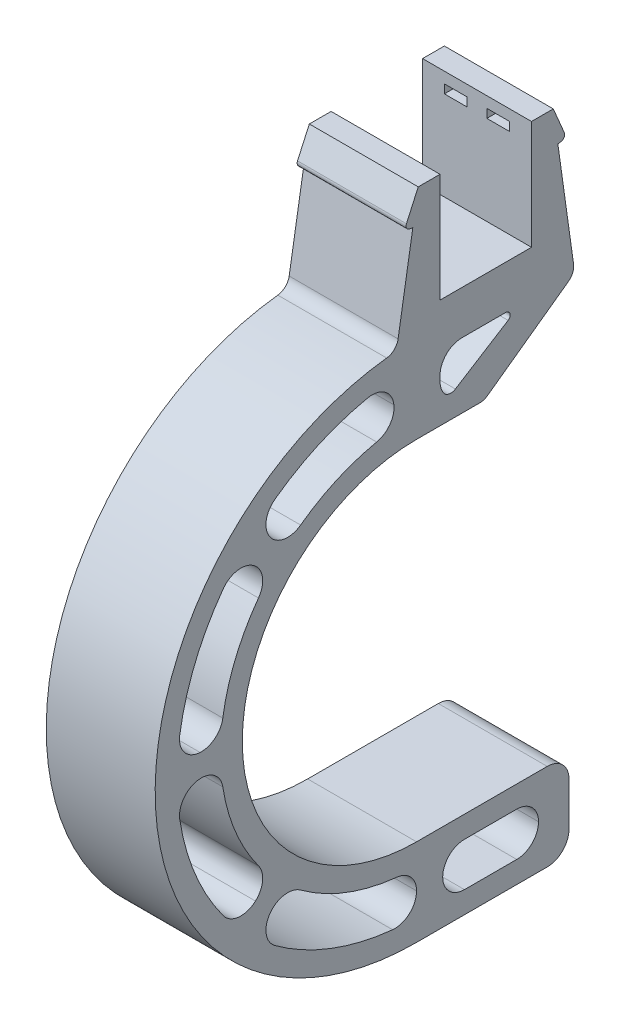
SolidWorks part; units mm, degrees
ref_plane "Front Plane" through (0, 0, 0) normal (0, 0, 1) x (1, 0, 0)
ref_plane "Top Plane" through (0, 0, 0) normal (0, 1, 0) x (1, 0, 0)
ref_plane "Right Plane" through (0, 0, 0) normal (1, 0, 0) x (0, 0, -1)
sketch "Sketch1" plane through (0, 0, 0) normal (1, 0, 0) x (0, 0, -1)
  line L0 (-10.1154, 7.5) -> (-10.1154, 32.5148)
  line L1 (-10.1154, 7.5) -> (10.8846, 7.5)
  line L2 (-15.5, -17.5) -> (0, -17.5)
  line L3 (0, -17.5) -> (20.8, -2.5)
  line L4 (-10.1154, -12.7739) -> (-10.1154, -2.5)
  line L5 (-15.1154, 32.5148) -> (-20.1154, 2.3222)
  line L6 (-15.5, -102.5) -> (-15.5, -112.5)
  line L7 (-10.1154, -2.5) -> (8.4637, -2.5)
  line L8 (8.4637, -2.5) -> (-7.9175, -12.7739)
  line L9 (-15.1154, 32.5148) -> (-10.1154, 32.5148)
  line L10 (15.8846, 32.5148) -> (20.8, -2.5)
  line L11 (-7.9175, -12.7739) -> (-10.1154, -12.7739)
  line L12 (-60.4383, -59.8551) -> (-70.4246, -60.3785)
  line L13 (15.8846, 32.5148) -> (10.8846, 32.5148)
  line L14 (-60.4383, -55.1449) -> (-70.4246, -54.6215)
  line L15 (10.8846, 7.5) -> (10.8846, 32.5148)
  line L16 (-48.9415, -27.3891) -> (-56.373, -20.6978)
  line L17 (-15.5, -117.5) -> (19.5, -117.5)
  line L18 (-15.5, -112.5) -> (-15.5, -102.5)
  line L19 (-15.5, -97.5) -> (19.5, -97.5)
  line L20 (19.5, -117.5) -> (19.5, -97.5)
  line L21 (-45.6109, -24.0585) -> (-52.3022, -16.627)
  line L22 (-20.2038, -12.7465) -> (-21.2491, -2.8013)
  line L23 (-48.9415, -87.6109) -> (-56.373, -94.3022)
  line L24 (-45.6109, -90.9415) -> (-52.3022, -98.373)
  line L26 (-9.5, -102.5) -> (12.5, -102.5)
  line L27 (-9.5, -102.5) -> (-9.5, -112.5)
  line L28 (-9.5, -112.5) -> (12.5, -112.5)
  line L29 (12.5, -102.5) -> (12.5, -112.5)
  arc A0 (-20.1154, 2.3222) -> (-15.5, -117.5) centre (-15.5, -57.5) ccw
  arc A1 (-15.5, -17.5) -> (-15.5, -97.5) centre (-15.5, -57.5) ccw
  arc A2 (-20.2038, -12.7465) -> (-45.6109, -24.0585) centre (-15.5, -57.5) ccw
  arc A3 (-21.2491, -2.8013) -> (-52.3022, -16.627) centre (-15.5, -57.5) ccw
  arc A4 (-48.9415, -27.3891) -> (-60.4383, -55.1449) centre (-15.5, -57.5) ccw
  arc A5 (-56.373, -20.6978) -> (-70.4246, -54.6215) centre (-15.5, -57.5) ccw
  arc A6 (-45.6109, -90.9415) -> (-15.5, -102.5) centre (-15.5, -57.5) ccw
  arc A7 (-52.3022, -98.373) -> (-15.5, -112.5) centre (-15.5, -57.5) ccw
  arc A8 (-70.4246, -60.3785) -> (-56.373, -94.3022) centre (-15.5, -57.5) ccw
  arc A9 (-60.4383, -59.8551) -> (-48.9415, -87.6109) centre (-15.5, -57.5) ccw
  point P0 (0, 0)
  dimension "D7" = 120
  dimension "D9" = 20
  dimension "D5" = 5
  dimension "D6" = 5
  dimension "D2" = 21
  dimension "D3" = 5
  dimension "D4" = 5
  dimension "D8" = 65
  dimension "D10" = 6
  dimension "D11" = 7
  dimension "D12" = 35
extrude "Boss-Extrude1" add sketch "Sketch1" against normal blind 25 contours A1 L2 L3 L10 L13 L15 L1 L0 L9 L5 A0 L17 L20 L19 A7 L24 A6 L6 A5 L16 A4 L14 A3 L22 A2 L21 L8 L11 L4 L7 L26 L29 L28 L27 L12 A9 L23 A8 region at (0, 5.7174, -0.3846)
fillet "Fillet1" radius 5 18 edges at (-12.5, -90.9415, 45.6109) (-12.5, -102.5, 9.5) (-12.5, -112.5, 9.5) (-12.5, -112.5, 15.5) (-12.5, -112.5, -12.5) (-12.5, -102.5, -12.5) (-12.5, -98.373, 52.3022) (-12.5, -102.5, 15.5) (-12.5, -87.6109, 48.9415) (-12.5, -94.3022, 56.373) (-12.5, -20.6978, 56.373) (-12.5, -27.3891, 48.9415) (-12.5, -55.1449, 60.4383) (-12.5, -54.6215, 70.4246) (-12.5, -16.627, 52.3022) (-12.5, -24.0585, 45.6109) (-12.5, -12.7465, 20.2038) (-12.5, -2.8013, 21.2491)
fillet "Fillet2" radius 5 2 edges at (-12.5, -59.8551, 60.4383) (-12.5, -60.3785, 70.4246)
fillet "Fillet3" radius 5 1 edges at (-12.5, -2.5, 10.1154)
fillet "Fillet4" radius 5 1 edges at (-12.5, -12.7739, 10.1154)
fillet "Fillet5" radius 2 1 edges at (-12.5, -12.7739, 7.9175)
fillet "Fillet6" radius 1 1 edges at (-12.5, -2.5, -8.4637)
fillet "Fillet7" radius 3 3 edges at (-12.5, -17.5, 0) (-12.5, -2.5, -20.8) (-12.5, 2.3222, 20.1154)
fillet "Fillet8" radius 5 2 edges at (-12.5, -117.5, -19.5) (-12.5, -97.5, -19.5)
sketch "Sketch2" plane through (0, 0, -10.8846) normal (0, 0, 1) x (1, 0, 0)
  line L0 (-25, 7.5) -> (0, 7.5) construction
  line L1 (-20, 30) -> (-14.75, 30)
  line L2 (-20, 30) -> (-20, 28)
  line L3 (-20, 28) -> (-14.75, 28)
  line L4 (-5, 30) -> (-5, 28)
  line L5 (-20, 30) -> (-14.75, 29.3) construction
  line L6 (-20, 28) -> (-14.75, 28.7) construction
  line L7 (0, 7.5) -> (0, 32.5148) construction
  line L8 (-10.25, 30) -> (-5, 30)
  line L10 (-14.75, 28) -> (-14.75, 30)
  line L12 (-10.25, 28) -> (-10.25, 30)
  line L15 (-10.25, 29.3) -> (-5, 30) construction
  line L16 (-10.25, 28.7) -> (-5, 28) construction
  line L17 (-10.25, 28) -> (-5, 28)
  point P0 (-12.5, 29)
  point P9 (-12.5, 24)
  dimension "D1" = 20.5
  dimension "D2" = 15
  dimension "D3" = 5
  dimension "D4" = 2
  dimension "D5" = 4.5
extrude "Cut-Extrude1" cut sketch "Sketch2" against normal blind 25 and the other way blind 35
sketch "Sketch3" plane through (0, 0, 0) normal (1, 0, 0) x (0, 0, -1)
  line L0 (16.9375, 25.0148) -> (18.9375, 25.2956)
  line L1 (15.8846, 32.5148) -> (20.5485, -0.7081) construction
  line L2 (18.9375, 25.2956) -> (15.8846, 32.5148)
  line L3 (15.8846, 32.5148) -> (16.9375, 25.0148)
  line L4 (-16.3574, 25.0148) -> (-18.3574, 25.346)
  line L5 (-15.1154, 32.5148) -> (-19.7386, 4.5973) construction
  line L6 (-18.3574, 25.346) -> (-15.1154, 32.5148)
  line L7 (-15.1154, 32.5148) -> (-16.3574, 25.0148)
  line L8 (15.8846, 32.5148) -> (10.8846, 32.5148) construction
  line L9 (-15.1154, 32.5148) -> (-10.1154, 32.5148) construction
  dimension "D1" = 2
  dimension "D2" = 2
  dimension "D3" = 7.5
  dimension "D4" = 7.5
extrude "Boss-Extrude2" add sketch "Sketch3" against normal blind 25
fillet "Fillet9" radius 1 2 edges at (-12.5, 25.2956, -18.9375) (-12.5, 25.346, 18.3574)
